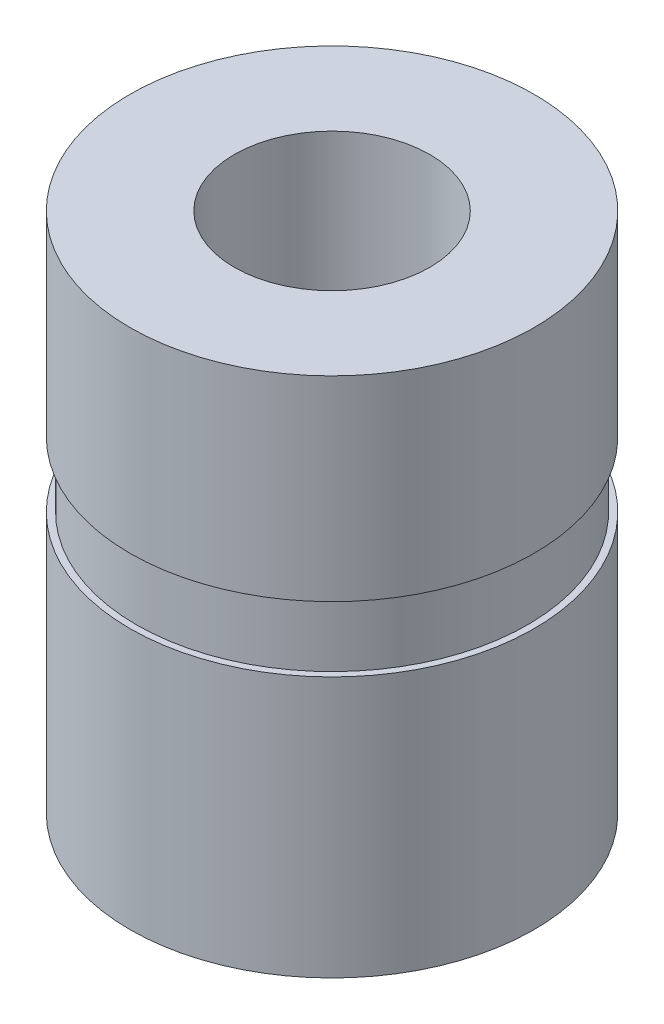
SolidWorks part; units mm, degrees
material "Ottone"
ref_plane "Piano frontale" through (0, 0, 0) normal (0, 0, 1) x (1, 0, 0)
ref_plane "Piano superiore" through (0, 0, 0) normal (0, 1, 0) x (1, 0, 0)
ref_plane "Piano destro" through (0, 0, 0) normal (1, 0, 0) x (0, 0, -1)
sketch "Schizzo1" plane through (0, 0, 0) normal (0, 1, 0) x (1, 0, 0)
  circle A0 centre (0, 0) radius 3.1
  circle A1 centre (0, 0) radius 3
  circle A2 centre (0, 0) radius 1.5
extrude "Estrusione-Estrusione1" add sketch "Schizzo1" along normal blind 4 contours A0
extrude "Estrusione-Estrusione2" add sketch "Schizzo1<3>" along normal blind 5 contours A1
sketch "Schizzo1<3>" plane through (0, 0, 0) normal (0, 1, 0) x (1, 0, 0) same geometry as "Schizzo1"
extrude "Estrusione-Estrusione3" add sketch "Schizzo1<4>" along normal blind 3 from surface contours A0 | A2 starting at face at (0, 5, 3)
sketch "Schizzo1<4>" plane through (0, 0, 0) normal (0, 1, 0) x (1, 0, 0) same geometry as "Schizzo1"
